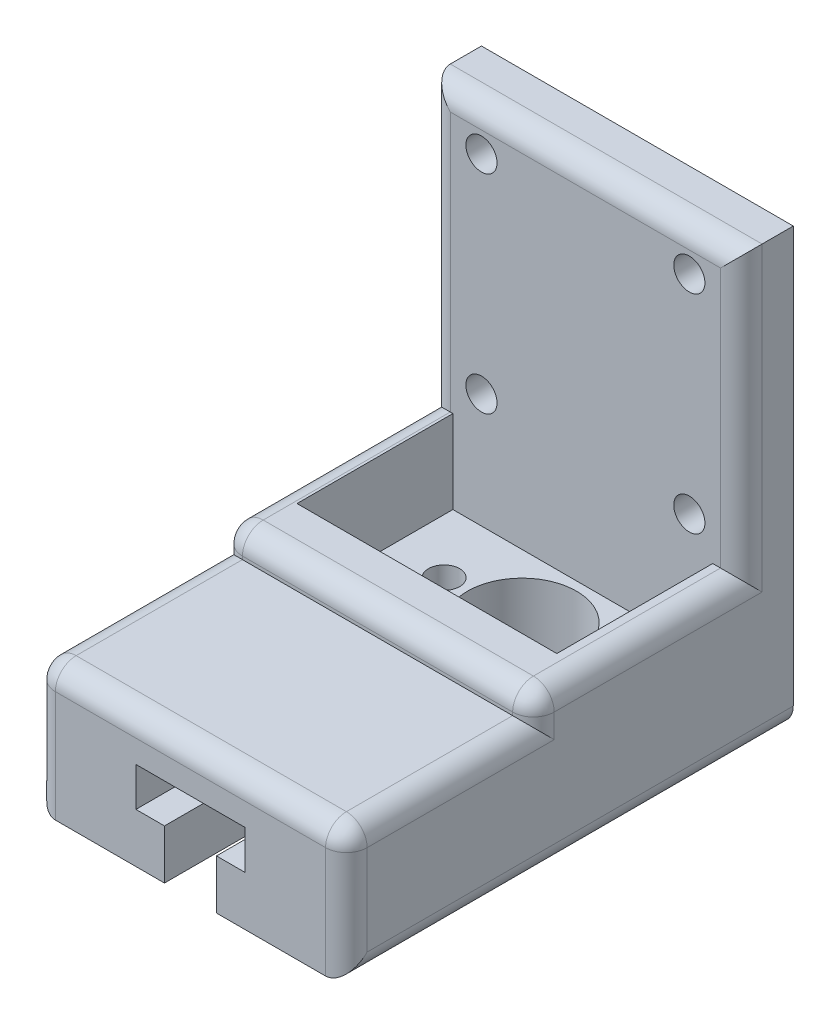
SolidWorks part; units mm, degrees
ref_plane "Front Plane" through (0, 0, 0) normal (0, 0, 1) x (1, 0, 0)
ref_plane "Top Plane" through (0, 0, 0) normal (0, 1, 0) x (1, 0, 0)
ref_plane "Right Plane" through (0, 0, 0) normal (1, 0, 0) x (0, 0, -1)
sketch "Sketch1" plane through (0, 0, 0) normal (0, 0, 1) x (1, 0, 0)
  line L1 (0, 0) -> (30, 0)
  line L2 (0, 0) -> (0, 15)
  line L3 (0, 15) -> (30, 15)
  line L4 (30, 0) -> (30, 15)
  dimension "D1" = 15
  dimension "D2" = 30
extrude "Boss-Extrude1" add sketch "Sketch1" along normal blind 20
sketch "Sketch2" plane through (0, 0, 0) normal (0, 0, -1) x (-1, 0, 0)
  line L0 (0, 0) -> (-30, 0) construction
  line L1 (-27.25, 0) -> (-2.25, 0)
  line L2 (-27.25, 0) -> (-27.25, 15)
  line L3 (-27.25, 15) -> (-2.25, 15)
  line L4 (-2.25, 0) -> (-2.25, 15)
  line L5 (0, 15) -> (0, 0) construction
  line L6 (-30, 0) -> (-30, 15) construction
  dimension "D1" = 25
  dimension "D2" = 2.25
  dimension "D3" = 15
  dimension "D4" = 2.75
extrude "Cut-Extrude1" cut sketch "Sketch2" against normal blind 15
sketch "Sketch3" plane through (0, 0, 20) normal (0, 0, 1) x (1, 0, 0)
  line L0 (0, 0) -> (30, 0) construction
  line L1 (0, 0) -> (30, 0)
  line L2 (0, 0) -> (0, 12.7)
  line L3 (0, 12.7) -> (30, 12.7)
  line L4 (30, 0) -> (30, 12.7)
  line L6 (0, 15) -> (0, 0) construction
  line L7 (30, 0) -> (30, 15) construction
  dimension "D3" = 12.7
extrude "Boss-Extrude2" add sketch "Sketch3" along normal blind 18
sketch "Sketch4" plane through (0, 0, 38) normal (0, 0, 1) x (1, 0, 0)
  line L0 (12.5, 0) -> (12.5, 4.7625)
  line L1 (0, 0) -> (30, 0) construction
  line L2 (12.5, 4.7625) -> (9.75, 4.7625)
  line L3 (9.75, 4.7625) -> (9.75, 8.5125)
  line L4 (9.75, 8.5125) -> (20.25, 8.5125)
  line L5 (20.25, 8.5125) -> (20.25, 4.7625)
  line L6 (20.25, 4.7625) -> (17.5, 4.7625)
  line L7 (17.5, 4.7625) -> (17.5, 0)
  line L8 (17.5, 0) -> (12.5, 0)
  line L10 (30, 0) -> (30, 12.7) construction
  line L11 (0, 12.7) -> (0, 0) construction
  point P10 (15, 8.5125)
  dimension "D1" = 10.5
  dimension "D2" = 3.75
  dimension "D3" = 2.75
  dimension "D4" = 2.75
  dimension "D5" = 4.7625
  dimension "D6" = 15
  dimension "D7" = 9.75
extrude "Cut-Extrude2" cut sketch "Sketch4" against normal blind 12.5
sketch "Sketch5" plane through (0, 0, 25.5) normal (0, 0, 1) x (1, 0, 0)
  line L1 (12.5, 0) -> (17.5, 0)
  line L2 (12.5, 0) -> (12.5, 4.7625)
  line L3 (12.5, 4.7625) -> (17.5, 4.7625)
  line L4 (17.5, 0) -> (17.5, 4.7625)
sketch "Sketch6" [suppressed] plane through (0, 0, 0) normal (0, 0, -1) x (-1, 0, 0)
  line L0 (-30, 0) -> (-30, 15) construction
  line L1 (-30, 8) -> (-27.75, 8)
  line L2 (-30, 8) -> (-30, 0)
  line L3 (-30, 0) -> (-27.75, 0)
  line L4 (-27.75, 8) -> (-27.75, 0)
  line L5 (-2.25, 0) -> (-2.25, 12.5) construction
  line L6 (-2.25, 8) -> (0, 8)
  line L7 (-2.25, 8) -> (-2.25, 0)
  line L8 (-2.25, 0) -> (0, 0)
  line L9 (0, 8) -> (0, 0)
  dimension "D1" = 8
  dimension "D2" = 8
extrude "Boss-Extrude4" [suppressed] add sketch "Sketch6" along normal blind 5
sketch "Sketch7" plane through (0, 15, 0) normal (0, 1, 0) x (1, 0, 0)
  line L0 (30, 0) -> (27.25, 0) construction
  line L1 (26.125, 8) -> (31.125, 8)
  line L2 (26.125, 8) -> (26.125, -8)
  line L3 (26.125, -8) -> (31.125, -8)
  line L4 (31.125, 8) -> (31.125, -8)
  line L5 (26.125, 8) -> (31.125, -8) construction
  line L6 (26.125, -8) -> (31.125, 8) construction
  circle A0 centre (28.625, -8) radius 2.5
  point P0 (28.625, 0)
  line M3 (30, 0) -> (27.25, 0)
  dimension "D1" = 5
  dimension "D2" = 8
extrude "Cut-Extrude3" [suppressed] cut sketch "Sketch7" against normal blind 5 contours L3 A0 | L3 A0 | A0 L4 L2 M3
sketch "Sketch8" [suppressed] plane through (30, 0, 0) normal (1, 0, 0) x (0, 0, -1)
  line L0 (2.5, 8) -> (2.5, 0) construction
  line L1 (5, 8) -> (0, 8) construction
  line L2 (-20, 0) -> (5, 0) construction
  circle A0 centre (2.5, 4) radius 1.375
  point P6 (2.5, 4)
  dimension "D1" = 2.75
extrude "Cut-Extrude4" [suppressed] cut sketch "Sketch8" against normal through all
chamfer "Chamfer1" [suppressed] distance 3 angle 45
sketch "Sketch9" plane through (30, 0, 0) normal (-1, 0, 0) x (0, 0, 1)
  line L0 (15, 0) -> (-5, 0)
  line L1 (-5, 0) -> (-5, 42)
  line L3 (-5, 42) -> (0, 42)
  line L4 (0, 42) -> (0, 7)
  line L5 (0, 15) -> (0, 0) construction
  line L6 (0, 7) -> (15, 7)
  line L7 (15, 15) -> (15, 0) construction
  line L8 (15, 7) -> (15, 0)
  dimension "D1" = 20
  dimension "D2" = 42
  dimension "D3" = 35
extrude "Boss-Extrude12" add sketch "Sketch9" along normal up to surface (30 mm away) up to face at (0, 9.2333, 19.3333)
sketch "Sketch10" plane through (0, 0, 0) normal (0, 0, 1) x (1, 0, 0)
  line L0 (0, 42) -> (0, 15) construction
  line L1 (5, 38) -> (25, 38)
  line L2 (5, 38) -> (5, 18)
  line L3 (5, 18) -> (25, 18)
  line L4 (25, 38) -> (25, 18)
  line L5 (0, 42) -> (30, 42) construction
  dimension "D1" = 20
  dimension "D2" = 20
  dimension "D3" = 5
  dimension "D4" = 4
hole_wizard "Ø2.5mm Dowel Hole1" positions "Sketch11" profile "Sketch12" hole size "Ø2.5" standard "ANSI Metric" end condition through all
sketch "Sketch11" plane through (0, 0, 0) normal (0, 0, 1) x (1, 0, 0)
  point P0 (5, 38)
  point P3 (25, 38)
  point P6 (5, 18)
  point P9 (25, 18)
sketch "Sketch12" plane through (5, 38, 0) normal (1, 0, 0) x (0, -1, 0)
  line L0 (0, 0) -> (0, 5)
  line L1 (0, 5) -> (1.5, 5)
  line L2 (1.5, 5) -> (1.5, 0)
  line L5 (1.5, 0) -> (0, 0)
  line L11 (0, -6.35) -> (0, 107.95) construction
  dimension "Thru Hole Dia." = 3
  dimension "Thru Hole Depth" = 5
sketch "Sketch13" plane through (0, 7, 0) normal (0, 1, 0) x (1, 0, 0)
  line L0 (0, 5) -> (30, 5) construction
  circle A0 centre (15, -6.1) radius 5.25
  circle A1 centre (22.5, -6.1) radius 1.5
  circle A2 centre (7.5, -6.1) radius 1.5
  point P8 (15, 5)
  dimension "D1" = 3
  dimension "D2" = 3
  dimension "D3" = 10.5
  dimension "D4" = 7.5
  dimension "D5" = 7.5
  dimension "D7" = 11.1
  dimension "D6" = 0
extrude "Cut-Extrude5" cut sketch "Sketch13" against normal through all
fillet "Fillet1" radius 2 15 edges at (0, 0, 16.5) (30, 0, 16.5) (15, 42, 0) (30, 28.5, 0) (0, 28.5, 0) (30, 15, 10) (0, 15, 10) (15, 15, 20) (0, 13.85, 20) (30, 13.85, 20) (0, 12.7, 29) (30, 12.7, 29) (0, 6.35, 38) (30, 6.35, 38) (15, 12.7, 38)
